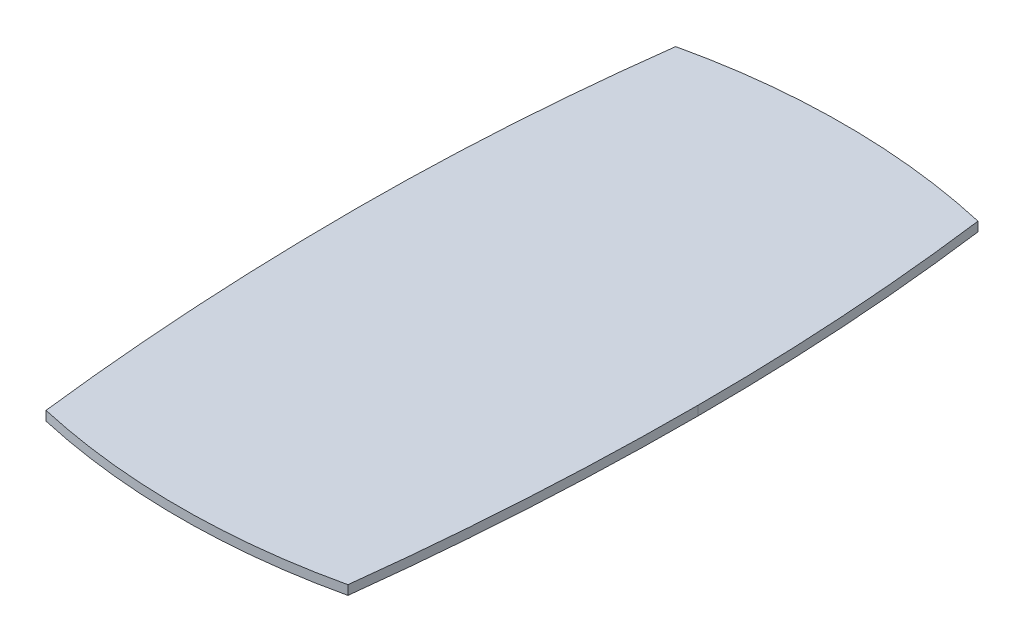
SolidWorks part; units mm, degrees
ref_plane "Front Plane" through (0, 0, 0) normal (0, 0, 1) x (1, 0, 0)
ref_plane "Top Plane" through (0, 0, 0) normal (0, 1, 0) x (1, 0, 0)
ref_plane "Right Plane" through (0, 0, 0) normal (1, 0, 0) x (0, 0, -1)
sketch "Sketch1" plane through (0, 0, 0) normal (0, 1, 0) x (1, 0, 0)
  line L1 (0, 0) -> (55, 0) construction
  line L3 (0, 107) -> (55, 107) construction
  line L4 (55, 0) -> (55, 107) construction
  line L5 (3.5, 107) -> (51.5, 107)
  line L6 (0, 107) -> (0, 0) construction
  line L7 (55, 3.5) -> (55, 103.5) construction
  line L8 (0, 56) -> (0, 103.5) construction
  line L9 (3.5, 0) -> (51.5, 0)
  line L10 (-108.8753, 12.2032) -> (-109.3305, 119.2022) construction
  arc A0 (3.1327, 104.2616) -> (27.5, 107) centre (27.5, -2.7857) cw
  arc A1 (27.5, 107) -> (51.8673, 104.2616) centre (27.5, -2.7857) cw
  arc A6 (51.8342, 2.7308) -> (27.5, 0) centre (27.5, 109.7857) cw
  arc A7 (3.1658, 2.7308) -> (27.5, 0) centre (27.5, 109.7857) ccw
  arc A8 (3.1327, 104.2616) -> (0, 56) centre (373.3214, 56) ccw
  arc A9 (0, 56) -> (3.1658, 2.7308) centre (449.75, 56) ccw
  arc A10 (51.8342, 2.7308) -> (55, 56) centre (-394.75, 56) ccw
  arc A11 (55, 56) -> (51.8673, 104.2616) centre (-318.3214, 56) ccw
  arc A12 (51.8673, 104.2616) -> (51.5, 107) centre (-318.3214, 56) ccw construction
  arc A13 (51.8673, 104.2616) -> (55, 103.5) centre (27.5, -2.7857) cw construction
  arc A14 (3.5, 107) -> (3.1327, 104.2616) centre (373.3214, 56) ccw construction
  arc A15 (3.15, 2.7344) -> (3.1658, 2.7308) centre (27.5, 109.7857) ccw construction
  arc A16 (51.5, 0) -> (51.8342, 2.7308) centre (-394.75, 56) ccw construction
  arc A17 (3.1658, 2.7308) -> (3.5, 0) centre (449.75, 56) ccw construction
  point P6 (0, 3.5)
  point P11 (27.5, 107)
  point P15 (27.5, 0)
  point P23 (55, 56)
  point P30 (0, 56)
  dimension "D1" = 107
  dimension "D2" = 55
  dimension "D3" = 56
  dimension "D4" = 48
  dimension "D5" = 48
  dimension "D6" = 100
  dimension "D10" = 3.5
  dimension "D11" = 56
extrude "Boss-Extrude1" add sketch "Sketch1" along normal blind 1.5 contours A7 A6 A1 A0 region at (27.5, 0, -53.5556)
sketch "Sketch2" plane through (0, 0, 0) normal (0, -1, 0) x (1, 0, 0)
  line L1 (15.75, -76.5) -> (39.25, -76.5)
  line L2 (15.75, -76.5) -> (15.75, -83)
  line L3 (15.75, -83) -> (39.25, -83)
  line L4 (39.25, -76.5) -> (39.25, -83)
  line L5 (15.75, -89.5) -> (39.25, -89.5)
  line L6 (15.75, -89.5) -> (15.75, -96)
  line L7 (15.75, -96) -> (39.25, -96)
  line L8 (39.25, -89.5) -> (39.25, -96)
  arc A0 (51.8342, -2.7308) -> (3.1658, -2.7308) centre (27.5, -109.7857) ccw construction
  arc A1 (3.1327, -104.2616) -> (51.8673, -104.2616) centre (27.5, 2.7857) ccw construction
  point P11 (27.5, 0)
  point P12 (27.5, -76.5)
  point P13 (27.5, -89.5)
  point P17 (27.5, -107)
  dimension "D1" = 23.5
  dimension "D2" = 23.5
  dimension "D3" = 6.5
  dimension "D4" = 17.5
  dimension "D5" = 6.5
extrude "Boss-Extrude2" add sketch "Sketch2" along normal blind 2 separate body contours L2 L1 L4 L3 | L6 L5 L8 L7
sketch "Sketch3" plane through (39.25, 0, 0) normal (1, 0, 0) x (0, 0, -1)
  line L0 (76.5, -2) -> (76.5, -9.5) construction
  line L1 (76.5, -2) -> (83, -2) construction
  line L2 (83, -2) -> (83, -9.5) construction
  line L3 (83, -9.5) -> (82.525, -9.6562)
  line L4 (83, -2) -> (82.4748, -2)
  line L5 (76.5, -2) -> (77.0252, -2)
  line L6 (76.975, -9.6563) -> (76.5, -9.5)
  line L7 (77.1711, -2.5) -> (82.3289, -2.5)
  line L8 (77.0252, -2) -> (82.4748, -2)
  line L9 (89.5, -2) -> (89.5, -9.5) construction
  line L10 (96, -2) -> (96, -9.5) construction
  line L11 (96, -9.5) -> (95.525, -9.6562)
  line L12 (96, -2) -> (95.5, -2)
  line L13 (89.5, -2) -> (90, -2)
  line L14 (89.9733, -9.6613) -> (89.5, -9.5)
  line L15 (90.1545, -2.5) -> (95.3455, -2.5)
  line L16 (90, -2) -> (95.5, -2)
  line L17 (89.5, -2) -> (96, -2) construction
  arc A0 (76.5, -2) -> (76.5, -9.5) centre (65.101, -5.75) cw
  arc A1 (83, -2) -> (83, -9.5) centre (94.399, -5.75) ccw
  arc A2 (77.0252, -2) -> (76.975, -9.6563) centre (65.101, -5.75) cw
  arc A3 (82.4748, -2) -> (82.525, -9.6562) centre (94.399, -5.75) ccw
  arc A4 (89.5, -2) -> (89.5, -9.5) centre (78.101, -5.75) cw
  arc A5 (76.975, -1.8437) -> (77.0252, -2) centre (65.101, -5.75) cw construction
  arc A6 (76.975, -1.8437) -> (76.975, -9.6563) centre (65.101, -5.75) cw construction
  arc A7 (82.525, -1.8438) -> (82.4748, -2) centre (94.399, -5.75) ccw construction
  arc A8 (82.525, -1.8438) -> (82.525, -9.6562) centre (94.399, -5.75) ccw construction
  arc A9 (96, -2) -> (96, -9.5) centre (107.399, -5.75) ccw
  arc A10 (90, -2) -> (89.9733, -9.6613) centre (78.6145, -5.791) cw
  arc A11 (95.5, -2) -> (95.525, -9.6562) centre (106.8855, -5.7909) ccw
  arc A12 (89.9749, -1.9256) -> (90, -2) centre (78.6145, -5.791) cw construction
  line M8 (76.5, -2) -> (83, -2)
  dimension "D2" = 12
  dimension "D3" = 12
  dimension "D7" = 0.5
  dimension "D12" = 12
  dimension "D13" = 12
  dimension "D1" = 7.5
  dimension "D6" = 0.5
  dimension "D8" = 0.5
  dimension "D9" = 0.5
  dimension "D10" = 0.5
  dimension "D11" = 7.5
  dimension "D14" = 0.5
  dimension "D4" = 0.5
  dimension "D5" = 0.5
extrude "Boss-Extrude3" add sketch "Sketch3" against normal blind 5.5 separate body contours A3 A2 L7 M8 | A11 L16 A10 L15 | L12 A11 L11 A9 | A2 L6 A0 L5 | L4 A1 L3 A3 | A10 L14 A4 L13 region at (39.25, -2.2477, -79.75) region at (39.25, -5.822, -95.3439) region at (39.25, -2.2476, -92.75)
extrude "Boss-Extrude4" add sketch "Sketch3<3>" along normal blind 5.5 from surface separate body contours A3 L3 A1 M8 | A3 A2 L7 M8 | A2 A0 L6 M8 | A10 L13 A4 L14 | A11 L16 A10 L15 | L12 A11 L11 A9 region at (39.25, -5.7905, -82.3492) region at (39.25, -2.2477, -79.75) region at (39.25, -5.7905, -77.1508) region at (39.25, -5.822, -95.3439) region at (39.25, -2.2476, -92.75) region at (39.25, -5.8233, -90.1559) starting at face at (15.75, -1, -92.75)
sketch "Sketch3<3>" plane through (39.25, 0, 0) normal (1, 0, 0) x (0, 0, -1) same geometry as "Sketch3"
ref_point "Point1"
ref_point "Point2"
ref_plane "Plane1" through (27.5, 0, 0) normal (1, 0, 0) x (0, 0, -1)
sketch "Sketch4" plane through (27.5, 0, 0) normal (1, 0, 0) x (0, 0, -1)
  line L0 (79.75, -2.5) -> (79.75, -7) construction
  line L1 (77.1711, -2.5) -> (82.3289, -2.5) construction
  line L2 (92.75, -2.5) -> (92.75, -7) construction
  line L3 (90.1545, -2.5) -> (95.3455, -2.5) construction
  line L4 (56, 0) -> (104.2616, 0) construction
  dimension "D1" = 7
